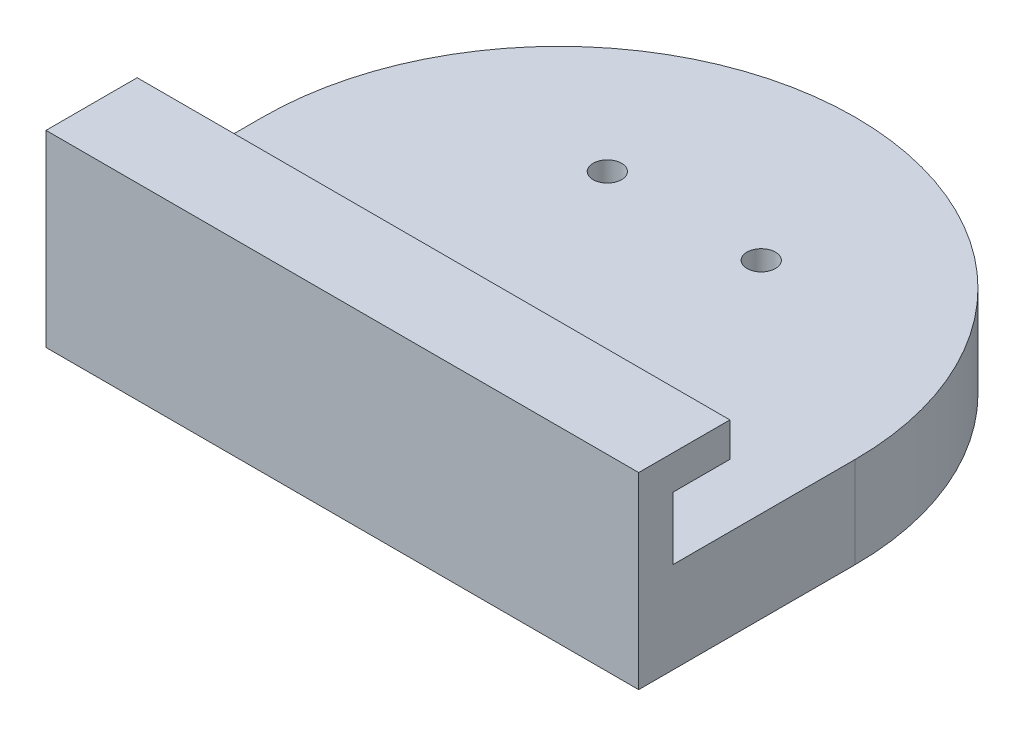
SolidWorks part; units mm, degrees
ref_plane "Front Plane" through (0, 0, 0) normal (0, 0, 1) x (1, 0, 0)
ref_plane "Top Plane" through (0, 0, 0) normal (0, 1, 0) x (1, 0, 0)
ref_plane "Right Plane" through (0, 0, 0) normal (1, 0, 0) x (0, 0, -1)
sketch "Sketch1" plane through (0, 0, 0) normal (0, 1, 0) x (1, 0, 0)
  line L0 (-26, 0) -> (-26, -19)
  line L1 (-26, -19) -> (26, -19)
  line L2 (26, -19) -> (26, 0)
  line L4 (-6.75, 11) -> (6.75, -11) construction
  line L17 (-6.75, -11) -> (6.75, 11) construction
  arc A0 (-26, 0) -> (26, 0) centre (0, 0) cw
  point P6 (0, 26)
  point P7 (0, 0)
  point P8 (0, 0)
  point P11 (0, 0)
  point P12 (0, 0)
  point P13 (-18.8732, 11)
  point P14 (0, 0)
  point P65 (-6.75, 11)
  point P66 (6.75, 11)
  point P67 (6.75, -11)
  point P68 (-6.75, -11)
  dimension "D1" = 26
  dimension "D2" = 45
  dimension "D3" = 22
  dimension "D4" = 13.5
extrude "Boss-Extrude1" add sketch "Sketch1" along normal blind 2
extrude "Boss-Extrude3" add sketch "Sketch1<3>" along normal blind 8 contours A0 L0 L1 L2 region at (0, 0, -1.1373)
sketch "Sketch1<3>" plane through (0, 0, 0) normal (0, 1, 0) x (1, 0, 0) same geometry as "Sketch1"
sketch "Sketch3" plane through (0, 0, 0) normal (1, 0, 0) x (0, 0, -1)
  line L0 (-19, 8) -> (-19, 16.5)
  line L1 (-19, 16.5) -> (-11, 16.5)
  line L2 (-11, 16.5) -> (-11, 13.5)
  line L3 (-11, 13.5) -> (-16, 13.5)
  line L4 (-16, 13.5) -> (-16, 8)
  line L6 (-16, 8) -> (-19, 8)
  point P6 (0, 0)
  point P8 (0, 0)
  point P9 (-15.9999, 8.0727)
  point P10 (0, 0)
  point P12 (-19, 8)
  dimension "D1" = 42
  dimension "D2" = 5.5
  dimension "D3" = 5
extrude "Boss-Extrude2" add sketch "Sketch3" along normal up to surface and the other way up to surface up to face at (26, 4, 9.5) other way up to face at (-26, 4, 9.5)
hole_wizard "Tap Drill for M3x0.5 Tap1" positions "Sketch4" profile "Sketch5" hole size "M3x0.5" standard "ANSI Metric" end condition up to next
sketch "Sketch4" plane through (0, 0, 0) normal (0, -1, 0) x (-1, 0, 0)
  point P0 (-6.75, 11)
  point P3 (6.75, 11)
  point P6 (6.75, -11)
  point P9 (-6.75, -11)
sketch "Sketch5" plane through (6.75, 0, -11) normal (1, 0, 0) x (0, 0, -1)
  line L0 (0, 0) -> (0, 8)
  line L1 (0, 8) -> (1.25, 8)
  line L2 (1.25, 8) -> (1.25, 0)
  line L5 (1.25, 0) -> (0, 0)
  line L11 (0, -6.35) -> (0, 107.95) construction
  dimension "Thru Hole Dia." = 2.5
  dimension "Thru Hole Depth" = 8
